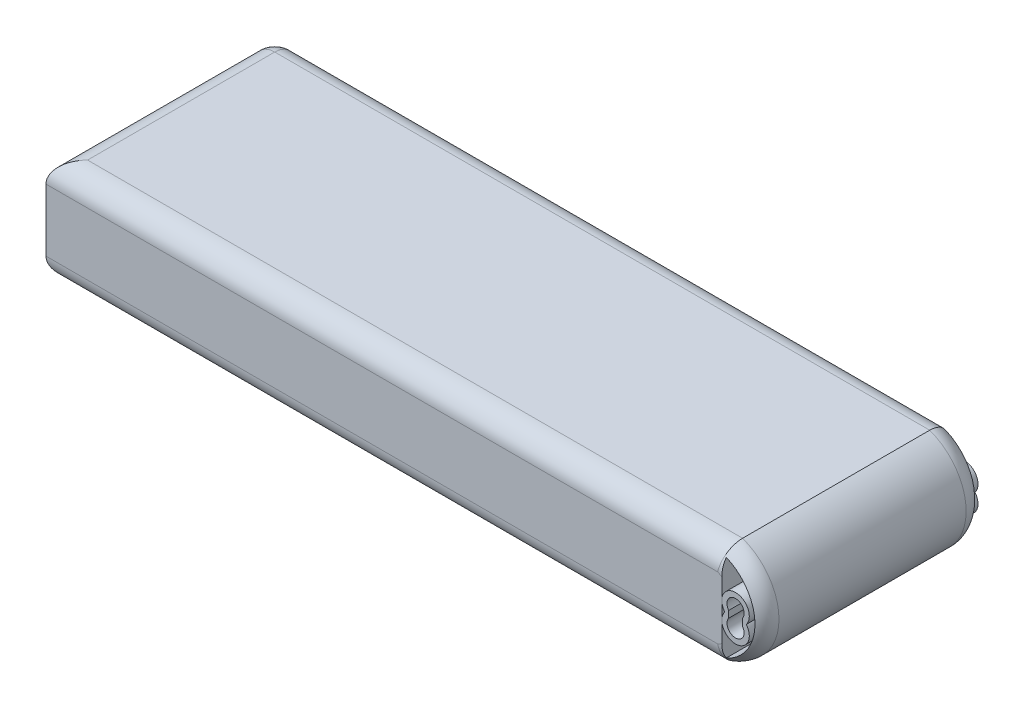
SolidWorks part; units mm, degrees
ref_plane "前视基准面" through (0, 0, 0) normal (0, 0, 1) x (1, 0, 0)
ref_plane "上视基准面" through (0, 0, 0) normal (0, 1, 0) x (1, 0, 0)
ref_plane "右视基准面" through (0, 0, 0) normal (1, 0, 0) x (0, 0, -1)
other "Configuration Table"
sketch "草图1" plane through (0, 0, 0) normal (0, 0, 1) x (1, 0, 0)
  line L0 (130, 20) -> (130, 0)
  line L1 (0, 0) -> (130, 0)
  line L2 (0, 0) -> (0, 20)
  line L3 (0, 20) -> (130, 20)
  arc A0 (130, 20) -> (130, 0) centre (126.3571, 10) cw
  arc A1 (130, 18.3858) -> (130, 1.6142) centre (126.3571, 10) cw
  arc A2 (129.4866, 18.5906) -> (129.4866, 1.4094) centre (126.3571, 10) cw construction
  point P1 (137, 10)
  dimension "D1" = 20
  dimension "D2" = 137
  dimension "D3" = 130
  dimension "D4" = 1.5
extrude "凸台-拉伸1" add sketch "草图1" along normal blind 44 contours L3 L2 L1 L0 | A0 L0 region at (136.7881, 10, 0) region at (65, 10, 0)
fillet "圆角1" radius 4 9 edges at (0, 10, 0) (65, 0, 0) (137, 10, 0) (65, 20, 0) (137, 10, 44) (65, 20, 44) (65, 0, 44) (0, 0, 22) (0, 20, 22)
sketch "草图2" plane through (0, 0, 44) normal (0, 0, 1) x (1, 0, 0)
  line L0 (130, 15.5549) -> (130, 4.4451) construction
  line L1 (130, 10) -> (135.5, 10) construction
  line L2 (131.3331, 10.652) -> (131.3331, 9.348)
  line L3 (133.9554, 10.652) -> (133.9554, 9.348)
  arc A2 (133.9554, 9.348) -> (131.3331, 9.348) centre (132.6443, 8.3557) cw
  arc A3 (133.9554, 10.652) -> (131.3331, 10.652) centre (132.6443, 11.6443) ccw
  arc A4 (133.9554, 9.348) -> (131.3331, 9.348) centre (132.6443, 11.6443) ccw
  arc A5 (130, 1.6142) -> (130, 18.3858) centre (126.3571, 10) ccw construction
  arc A6 (133.9554, 10.652) -> (131.3331, 10.652) centre (132.6443, 8.3557) cw
  dimension "D2" = 1
extrude "凸台-拉伸2" add sketch "草图2" against normal up to surface (44 mm away) separate body contours A6 A4 A2 | L1 A4 L2 | A6 L1 L2 | L3 L1 A6 | L1 L3 A4 | A4 A6 A3 region at (131.064, 10.2314, 44) region at (131.064, 9.7686, 44) region at (130.8778, 9.586, 44) region at (132.6443, 14.2205, 44) region at (134.2246, 9.7686, 44) region at (134.2246, 10.2314, 44) up to face at (87.7385, 10, 0)
other "连接点1" parameters "直径"=5, "端头长度"=3
ref_axis "基准轴1" through (132.6443, 11.6443, -10) along (0, 0, 1)
other "连接点2" parameters "直径"=5, "端头长度"=3
ref_axis "基准轴2" through (132.6443, 8.3557, 54) along (0, 0, -1)
other "连接点3" parameters "直径"=5, "端头长度"=3
ref_axis "基准轴3" through (132.6443, 8.3557, -10) along (0, 0, 1)
other "连接点4" parameters "直径"=5, "端头长度"=3
ref_axis "基准轴4" through (132.6443, 11.6443, 54) along (0, 0, -1)
